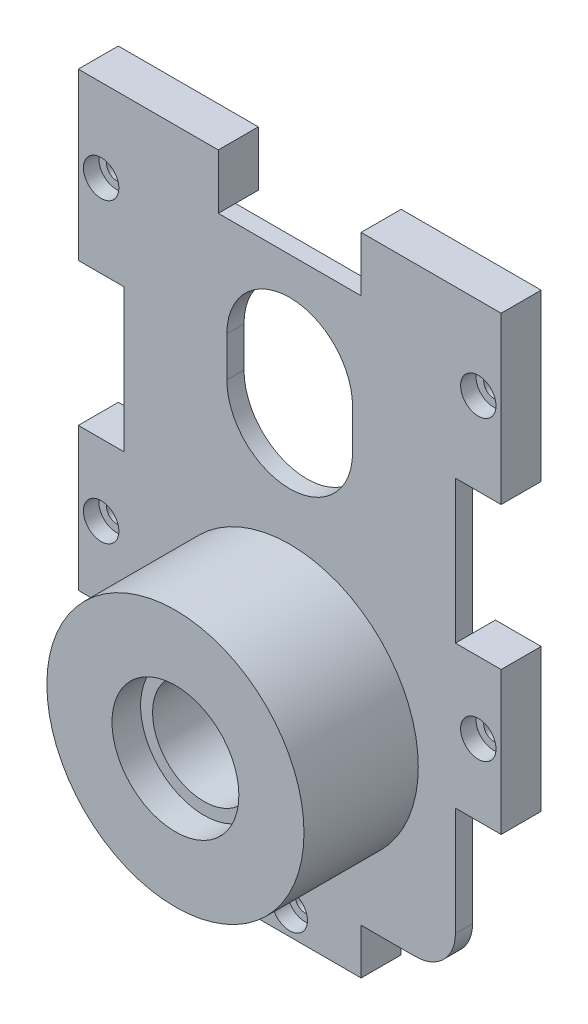
SolidWorks part; units mm, degrees
ref_plane "Alzado" through (0, 0, 0) normal (0, 0, 1) x (1, 0, 0)
ref_plane "Planta" through (0, 0, 0) normal (0, 1, 0) x (1, 0, 0)
ref_plane "Vista lateral" through (0, 0, 0) normal (1, 0, 0) x (0, 0, -1)
sketch "Croquis2" plane through (0, 0, 0) normal (0, 0, 1) x (1, 0, 0)
  line L0 (-30.7866, 48.816) -> (-5.7866, 48.816)
  line L1 (-5.7866, 48.816) -> (-5.7866, 39.2053)
  line L2 (-5.7866, 39.2053) -> (-30.7866, 39.2053)
  line L3 (-30.7866, 48.816) -> (-30.7866, 39.2053)
  line L5 (-22.5241, 25.0911) -> (-22.5241, 24.7943)
  line L7 (-18.1703, 25.0911) -> (-18.1703, 24.7943)
  line L8 (-5.7866, 48.816) -> (18.7134, 48.816)
  line L9 (-55.2866, 48.816) -> (-30.7866, 48.816)
  line L10 (18.7134, 48.816) -> (18.7134, 19.816)
  line L11 (-55.2866, 48.816) -> (-55.2866, 19.816)
  line L12 (-55.2866, 19.816) -> (-47.2866, 19.816)
  line L13 (-47.2866, 19.816) -> (-47.2866, 39.2053)
  line L14 (-47.2866, 39.2053) -> (-30.7866, 39.2053)
  line L15 (18.7134, 19.816) -> (10.7134, 19.816)
  line L16 (10.7134, 19.816) -> (10.7134, 39.2053)
  line L17 (10.7134, 39.2053) -> (-5.7866, 39.2053)
  line L18 (-55.2866, 19.816) -> (-55.2866, -5.184)
  line L19 (-55.2866, -5.184) -> (-47.2866, -5.184)
  line L20 (-47.2866, -5.184) -> (-47.2866, 19.816)
  line L21 (10.7134, 19.816) -> (10.7134, -5.184)
  line L22 (18.7134, 19.816) -> (18.7134, -5.184)
  line L23 (10.7134, -5.184) -> (18.7134, -5.184)
  line L24 (-55.2866, -5.184) -> (-55.2866, -30.184)
  line L25 (18.7134, -5.184) -> (18.7134, -30.184)
  line L26 (-47.2866, -5.184) -> (-47.2866, -30.184)
  line L28 (10.7134, -5.184) -> (10.7134, -30.184)
  line L29 (-55.2866, -30.184) -> (-47.2866, -30.184)
  line L30 (18.7134, -30.184) -> (10.7134, -30.184)
  line L31 (-55.2866, -30.184) -> (-55.2866, -49.184)
  line L32 (18.7134, -30.184) -> (18.7134, -49.184)
  line L34 (-47.2866, -30.184) -> (-47.2866, -49.184)
  line L35 (10.7134, -30.184) -> (10.7134, -49.184)
  line L36 (-47.2866, -49.184) -> (-55.2866, -49.184)
  line L37 (10.7134, -49.184) -> (18.7134, -49.184)
  line L38 (-40.2866, -56.184) -> (-30.7866, -56.184)
  line L39 (3.7134, -56.184) -> (3.7134, -64.184)
  line L40 (-30.7866, -56.184) -> (-30.7866, -64.184)
  line L42 (-30.7866, -64.184) -> (-40.2866, -64.184)
  line L43 (-30.7866, -56.184) -> (-5.7866, -56.184)
  line L44 (-40.2866, -64.184) -> (-40.2866, -56.184)
  line L45 (-5.7866, -56.184) -> (-5.7866, -64.184)
  line L46 (-5.7866, -64.184) -> (-30.7866, -64.184)
  line L47 (3.7134, -64.184) -> (-5.7866, -64.184)
  line L48 (-5.7866, -56.184) -> (3.7134, -56.184)
  line L50 (-7.2866, 21.7053) -> (-7.2866, 14.7053)
  line L52 (-29.2866, 21.7053) -> (-29.2866, 14.7053)
  arc A0 (-55.2866, -49.184) -> (-40.2866, -64.184) centre (-40.2866, -49.184) ccw
  arc A1 (18.7134, -49.184) -> (3.7134, -64.184) centre (3.7134, -49.184) cw
  arc A2 (-47.2866, -49.184) -> (-40.2866, -56.184) centre (-40.2866, -49.184) ccw
  arc A3 (3.7134, -56.184) -> (10.7134, -49.184) centre (3.7134, -49.184) ccw
  circle A4 centre (-18.2866, -27.184) radius 9
  arc A5 (-7.2866, 21.7053) -> (-29.2866, 21.7053) centre (-18.2866, 21.7053) ccw
  arc A7 (-29.2866, 14.7053) -> (-7.2866, 14.7053) centre (-18.2866, 14.7053) ccw
  circle A16 centre (-18.2866, -27.184) radius 22.5
  circle A17 centre (-18.2866, -27.184) radius 11.1
extrude "Saliente-Extruir1" add sketch "Croquis2" along normal blind 7 contours L48 A3 L35 L28 L21 L16 L17 L2 L14 L13 L20 L26 L34 A2 L38 L43 A16 A7 L52 A5 L50 | L17 L16 L15 L10 L8 L1 | L13 L14 L3 L9 L11 L12 | L24 L29 L26 L19 | L46 L45 L43 L40 | L30 L25 L23 L28 region at (-31.1663, 44.0106, 0) region at (6.4634, 48.4364, 0) region at (-18.2866, -3.6342, 0) region at (-51.2866, -17.684, 0) region at (14.7134, -17.684, 0) region at (-18.2866, -60.184, 0)
extrude "Saliente-Extruir2" add sketch "Croquis2<4>" along normal blind 22 separate body contours A17 A4 region at (-29.0727, -27.184, 0)
sketch "Croquis2<4>" plane through (0, 0, 0) normal (0, 0, 1) x (1, 0, 0) same geometry as "Croquis2"
extrude "Saliente-Extruir3" add sketch "Croquis2<5>" along normal blind 27 contours A16 A17 region at (-40.1502, -27.184, 0)
sketch "Croquis2<5>" plane through (0, 0, 0) normal (0, 0, 1) x (1, 0, 0) same geometry as "Croquis2"
sketch "Croquis3" plane through (0, 0, 7) normal (0, 0, 1) x (1, 0, 0)
  circle A0 centre (-51.2866, 34.316) radius 1.75
  circle A1 centre (-51.2866, -17.684) radius 1.75
  circle A2 centre (-18.2866, -60.184) radius 1.75
  circle A3 centre (14.7134, -17.684) radius 1.75
  circle A4 centre (14.7134, 34.316) radius 1.75
extrude "Cortar-Extruir1" cut sketch "Croquis3" against normal blind 7
sketch "Croquis4" plane through (0, 0, 7) normal (0, 0, 1) x (1, 0, 0)
  circle A0 centre (-51.2866, -17.684) radius 3.1
  circle A1 centre (-51.2866, 34.316) radius 3.1
  circle A2 centre (14.7134, 34.316) radius 3.1
  circle A3 centre (14.7134, -17.684) radius 3.1
  circle A4 centre (-18.2866, -60.184) radius 3.1
extrude "Cortar-Extruir2" cut sketch "Croquis4" against normal blind 2.7
sketch "Croquis5" plane through (0, 0, 0) normal (0, 0, -1) x (-1, 0, 0)
  line L1 (30.7866, 39.2053) -> (47.2866, 39.2053)
  line L2 (30.7866, 39.2053) -> (30.7866, 19.816)
  line L3 (30.7866, 19.816) -> (47.2866, 19.816)
  line L4 (47.2866, 39.2053) -> (47.2866, 19.816)
  line L5 (-10.7134, 19.816) -> (5.7866, 19.816)
  line L6 (-10.7134, 19.816) -> (-10.7134, 39.2053)
  line L7 (-10.7134, 39.2053) -> (5.7866, 39.2053)
  line L8 (5.7866, 19.816) -> (5.7866, 39.2053)
  line L9 (-10.7134, 39.2053) -> (47.2866, 39.2053)
  line L10 (-10.7134, 39.2053) -> (-10.7134, -49.184)
  line L11 (-10.7134, -49.184) -> (47.2866, -49.184)
  line L12 (47.2866, 39.2053) -> (47.2866, -49.184)
  line L13 (-10.7134, -49.184) -> (47.2866, -49.184)
  line L14 (-10.7134, -49.184) -> (-10.7134, -56.184)
  line L15 (-10.7134, -56.184) -> (47.2866, -56.184)
  line L16 (47.2866, -49.184) -> (47.2866, -56.184)
  line M6 (-10.7134, 19.816) -> (-10.7134, -5.184)
  line M10 (-10.7134, -30.184) -> (-10.7134, -49.184)
  arc M11 (-10.7134, -49.184) -> (-3.7134, -56.184) centre (-3.7134, -49.184) ccw
  line M12 (-3.7134, -56.184) -> (5.7866, -56.184)
  line M16 (30.7866, -56.184) -> (40.2866, -56.184)
  arc M17 (40.2866, -56.184) -> (47.2866, -49.184) centre (40.2866, -49.184) ccw
  line M18 (47.2866, -49.184) -> (47.2866, -30.184)
  line M22 (47.2866, -5.184) -> (47.2866, 19.816)
  line M27 (30.7866, 39.2053) -> (5.7866, 39.2053)
  arc M32 (29.2866, 14.7053) -> (7.2866, 14.7053) centre (18.2866, 14.7053) cw
  line M33 (7.2866, 14.7053) -> (7.2866, 21.7053)
  arc M34 (7.2866, 21.7053) -> (29.2866, 21.7053) centre (18.2866, 21.7053) cw
  line M35 (29.2866, 21.7053) -> (29.2866, 14.7053)
  circle M36 centre (18.2866, -27.184) radius 9
extrude "Cortar-Extruir3" cut sketch "Croquis5" against normal blind 4 contours L12 L3 L2 L8 L5 L10 L11 M22 M27 M6 M10 M18 M36 M35 M32 M33 M34 | L5 L8 L7 L6 | L4 L1 L2 L3 | L15 L11 M12 M16 M17 M11 region at (-39.0366, 29.5106, 0) region at (-18.2866, -12.7814, 0) region at (2.4634, 29.5106, 0) region at (-18.2866, -52.5782, 0)
